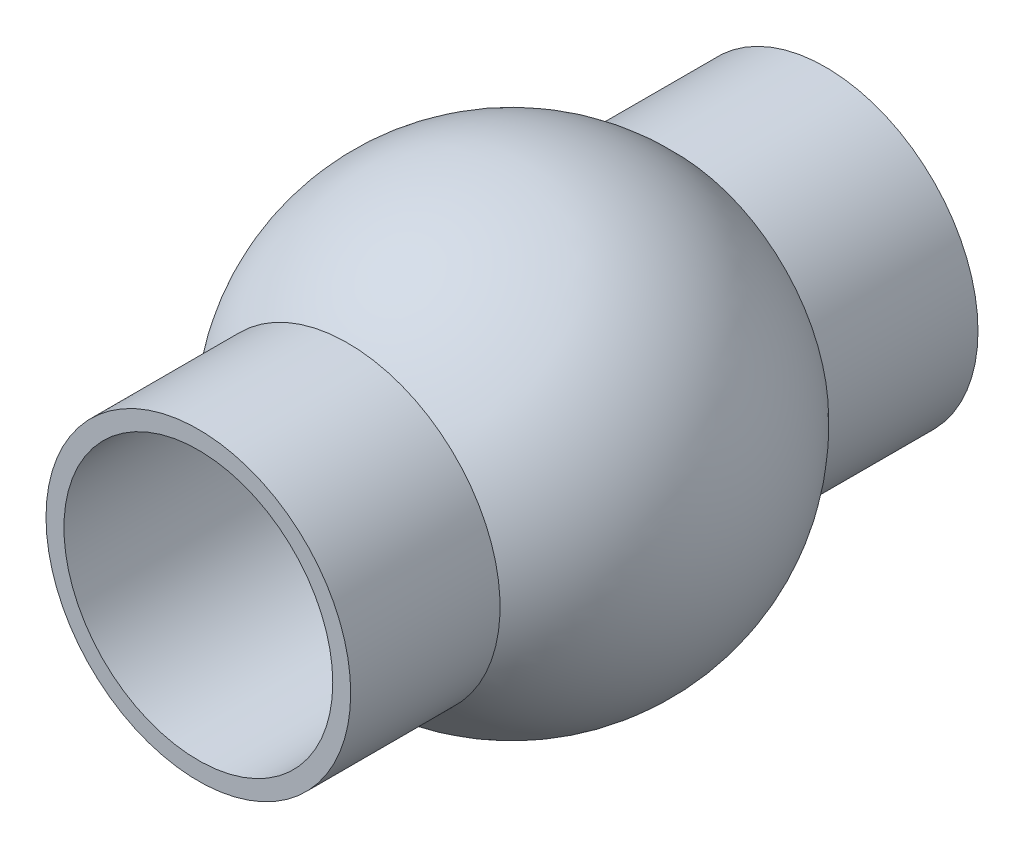
SolidWorks part; units mm, degrees
ref_plane "Front Plane" through (0, 0, 0) normal (0, 0, 1) x (1, 0, 0)
ref_plane "Top Plane" through (0, 0, 0) normal (0, 1, 0) x (1, 0, 0)
ref_plane "Right Plane" through (0, 0, 0) normal (1, 0, 0) x (0, 0, -1)
sketch "Sketch1" plane through (0, 0, 0) normal (0, 0, 1) x (1, 0, 0)
  line L0 (0, 2.5) -> (0, -2.5)
  circle A0 centre (0, 0) radius 2.5
  dimension "D1" = 5
ref_axis "Axis1" through (0, 2.75, 0) along (0, -1, 0)
revolve "Revolve1" add sketch "Sketch1" angle 360 about axis through (0, 2.75, 0) along (0, -1, 0) region at (1.061, 0, 0)
sketch "Sketch2" plane through (0, 0, 0) normal (0, 0, 1) x (1, 0, 0)
  circle A0 centre (0, 0) radius 1.5
  circle A1 centre (0, 0) radius 1.7
  dimension "D1" = 3
  dimension "D2" = 0.2
extrude "Cut-Extrude1" cut sketch "Sketch2" against normal through all both and the other way through all contours A0 region at (0, 0, 0)
extrude "Boss-Extrude1" add sketch "Sketch2<3>" along normal mid plane 7
sketch "Sketch2<3>" plane through (0, 0, 0) normal (0, 0, 1) x (1, 0, 0) same geometry as "Sketch2"
